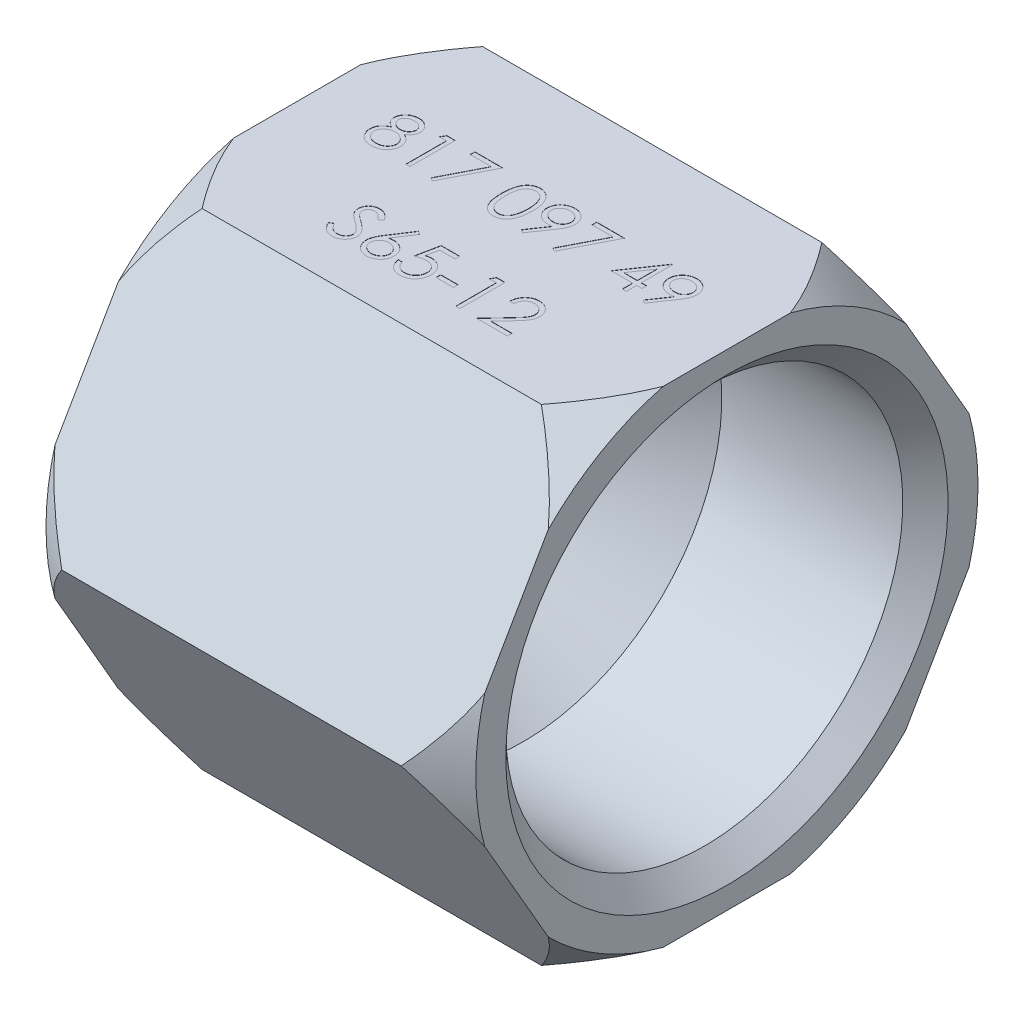
SolidWorks part; units mm, degrees
material "4140 H/T"
ref_plane "Front Plane" through (0, 0, 0) normal (0, 0, 1) x (1, 0, 0)
ref_plane "Top Plane" through (0, 0, 0) normal (0, 1, 0) x (1, 0, 0)
ref_plane "Right Plane" through (0, 0, 0) normal (1, 0, 0) x (0, 0, -1)
sketch "Sketch1" plane through (0, 0, 0) normal (0, 0, 1) x (1, 0, 0)
  line L0 (0, 0) -> (32.0688, 0) construction
  line L1 (0, 0) -> (0, 11.1)
  line L2 (0, 11.1) -> (2, 12.4)
  line L3 (2, 12.4) -> (17, 12.4)
  line L4 (17, 12.4) -> (19, 11.1)
  line L5 (19, 11.1) -> (19, 8.775)
  line L6 (19, 8.775) -> (10, 8.775)
  line L7 (10, 8.775) -> (5, 5)
  line L9 (0, 0) -> (1.9957, 0)
  line L11 (5, 5) -> (1.9957, 0)
  dimension "D1" = 10
  dimension "D2" = 14
  dimension "D3" = 19
  dimension "D4" = 22.2
  dimension "D5" = 24.8
  dimension "D7" = 2
  dimension "D6" = 2
  dimension "D8" = 17.55
  dimension "D9" = 9
  dimension "D10" = 59
revolve "Revolve1" add sketch "Sketch1" angle 360 about L0
sketch "Sketch2" plane through (19, 0, 0) normal (1, 0, 0) x (0, 0, -1)
  line L1 (6.2, 10.7387) -> (-6.2, 10.7387)
  line L2 (-6.2, 10.7387) -> (-12.4, 0)
  line L3 (-12.4, 0) -> (-6.2, -10.7387)
  line L4 (-6.2, -10.7387) -> (6.2, -10.7387)
  line L5 (6.2, -10.7387) -> (12.4, 0)
  line L6 (12.4, 0) -> (6.2, 10.7387)
  circle A0 centre (0, 0) radius 10.7387 construction
  circle A1 centre (0, 0) radius 12.4 construction
extrude "Extrude1" cut sketch "Sketch2" against normal up to surface (19 mm away) flip side to cut up to face at (0, 0, 11.1)
chamfer "Chamfer1" distance 1 angle 45 1 edges at (19, 0, 8.775)
sketch "Sketch3" plane through (0, 10.7387, 0) normal (0, 1, 0) x (1, 0, 0)
  line L0 (0, 0) -> (19, 0) construction
  line L1 (19, -2.8089) -> (19, 2.8089) construction
  text T0 "817 097 49\r\nS65-12" font "Century Gothic" height 2
extrude "Cut-Extrude1" cut sketch "Sketch3" against normal blind 0.01
